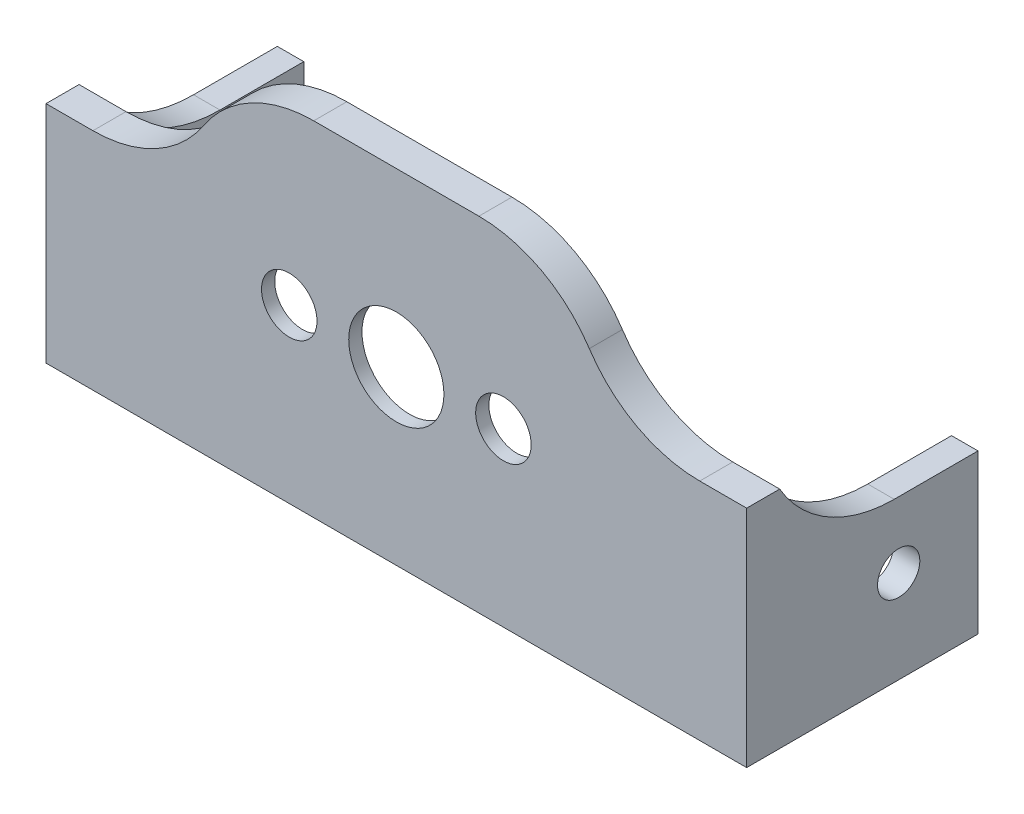
SolidWorks part; units mm, degrees
ref_plane "Front Plane" through (0, 0, 0) normal (0, 0, 1) x (1, 0, 0)
ref_plane "Top Plane" through (0, 0, 0) normal (0, 1, 0) x (1, 0, 0)
ref_plane "Right Plane" through (0, 0, 0) normal (1, 0, 0) x (0, 0, -1)
sketch "Sketch3" plane through (0, 0, 0) normal (0, 0, 1) x (1, 0, 0)
  line L0 (1.1713, 11.1422) -> (1.1713, -14.8578) construction
  line L1 (-11.8287, 11.1422) -> (14.1713, 11.1422)
  line L2 (-25.3287, 2.1422) -> (-25.3287, -14.8578)
  line L3 (-25.3287, -14.8578) -> (27.6713, -14.8578)
  line L4 (27.6713, 2.1422) -> (27.6713, -14.8578)
  line L5 (-11.8287, 11.1422) -> (-11.8287, 2.1422)
  line L6 (-11.8287, 2.1422) -> (-25.3287, 2.1422)
  line L7 (14.1713, 2.1422) -> (27.6713, 2.1422)
  line L8 (14.1713, 11.1422) -> (14.1713, 2.1422)
  dimension "D1" = 26
  dimension "D2" = 53
  dimension "D3" = 13
  dimension "D4" = 17
extrude "Boss-Extrude1" add sketch "Sketch3" along normal blind 2.5
sketch "Sketch4" plane through (0, 0, 0) normal (0, 0, -1) x (-1, 0, 0)
  line L0 (-14.1713, 11.1422) -> (11.8287, 11.1422) construction
  line L1 (25.3287, 2.1422) -> (25.3287, -14.8578) construction
  circle A0 centre (-1.1713, -1.8578) radius 12.55
  dimension "D1" = 25.1
  dimension "D3" = 26.5
  dimension "D2" = 13
extrude "Cut-Extrude1" cut sketch "Sketch4" against normal blind 1.5
sketch "Sketch5" plane through (0, 0, 1.5) normal (0, 0, -1) x (-1, 0, 0)
  line L0 (-1.1713, 12.511) -> (-1.1713, -1.8578) construction
  line L1 (-14.1713, 11.1422) -> (11.8287, 11.1422) construction
  circle A0 centre (-9.2713, -1.8578) radius 2.1
  circle A1 centre (6.9287, -1.8578) radius 2.1
  circle A2 centre (-1.1713, -1.8578) radius 3.6
  dimension "D1" = 16.2
  dimension "D2" = 4.2
  dimension "D3" = 7.2
  dimension "D4" = 13
extrude "Cut-Extrude2" cut sketch "Sketch5" against normal up to next
sketch "Sketch8" plane through (0, 0, 0) normal (0, 0, -1) x (-1, 0, 0)
  line L0 (25.3287, -14.8578) -> (-27.6713, -14.8578) construction
  line L1 (-27.6713, -2.8578) -> (-25.6713, -2.8578)
  line L2 (-27.6713, -2.8578) -> (-27.6713, -14.8578)
  line L3 (-27.6713, -14.8578) -> (-25.6713, -14.8578)
  line L4 (-25.6713, -2.8578) -> (-25.6713, -14.8578)
  line L5 (-1.1713, 11.1422) -> (-1.1713, -21.1015) construction
  line L6 (-14.1713, 11.1422) -> (11.8287, 11.1422) construction
  line L11 (25.3287, -14.8578) -> (23.3287, -14.8578)
  line L12 (23.3287, -2.8578) -> (23.3287, -14.8578)
  line L13 (25.3287, -2.8578) -> (23.3287, -2.8578)
  line L14 (25.3287, -2.8578) -> (25.3287, -14.8578)
  line L15 (-27.6713, -14.8578) -> (-27.6713, 2.1422) construction
  dimension "D1" = 2
  dimension "D2" = 12
extrude "Boss-Extrude3" add sketch "Sketch8" along normal blind 15
fillet "Fillet3" radius 10 4 edges at (-11.8287, 2.1422, 1.25) (14.1713, 2.1422, 1.25) (-24.3287, -2.8578, 0) (26.6713, -2.8578, 0)
fillet "Fillet4" radius 10 2 edges at (14.1713, 11.1422, 1.25) (-11.8287, 11.1422, 1.25)
sketch "Sketch9" plane through (27.6713, 0, 0) normal (1, 0, 0) x (0, 0, -1)
  line L0 (-2.5, -14.8578) -> (15, -14.8578) construction
  line L1 (15, -2.8578) -> (15, -14.8578) construction
  circle A0 centre (9, -7.8578) radius 1.6
  dimension "D1" = 3.2
  dimension "D2" = 7
  dimension "D3" = 6
extrude "Cut-Extrude3" cut sketch "Sketch9" against normal through all
